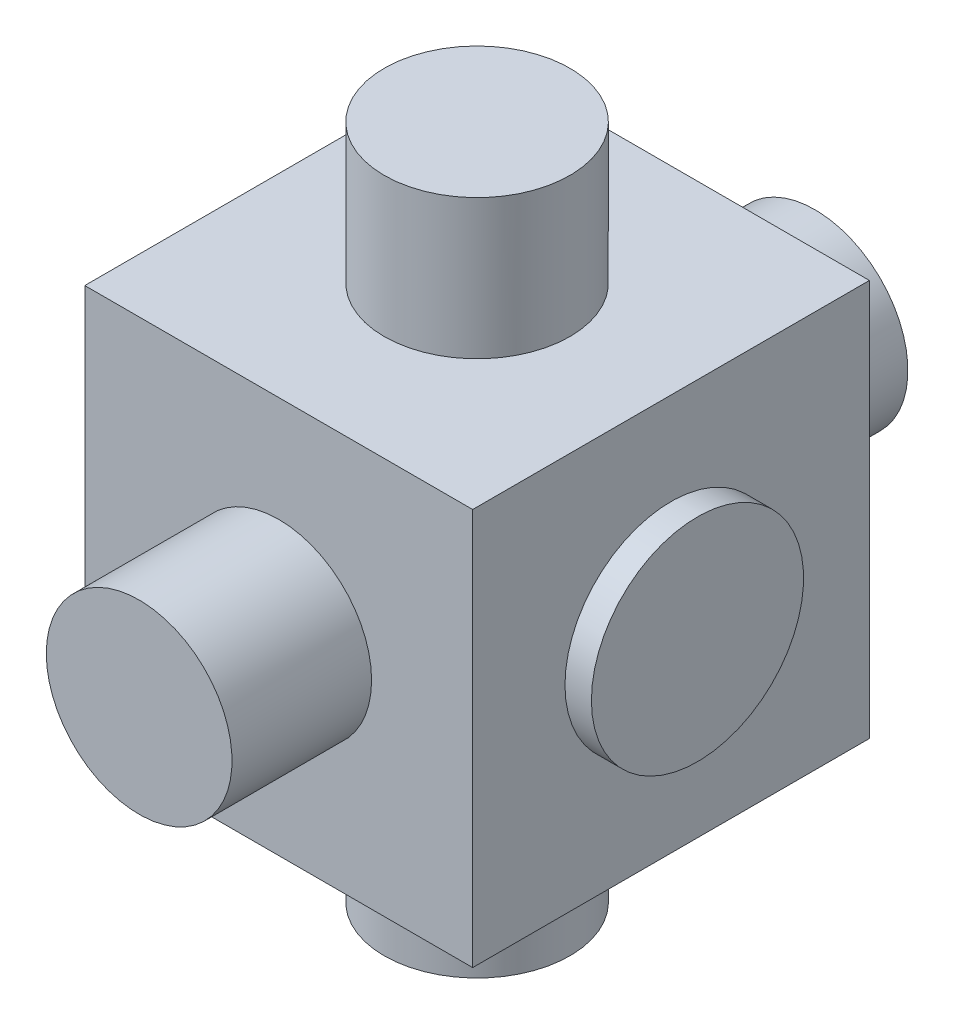
SolidWorks part; units mm, degrees
ref_plane "Front Plane" through (0, 0, 0) normal (0, 0, 1) x (1, 0, 0)
ref_plane "Top Plane" through (0, 0, 0) normal (0, 1, 0) x (1, 0, 0)
ref_plane "Right Plane" through (0, 0, 0) normal (1, 0, 0) x (0, 0, -1)
ref_plane "Plane1" through (0, 0, 0) normal (0, 0, 1) x (1, 0, 0)
sketch "Sketch1" plane through (0, 0, 0) normal (0, 0, 1) x (1, 0, 0)
  line L0 (19.4, 6.75) -> (19.4, -6.75)
  line L1 (19.4, -6.75) -> (32.6, -6.75)
  line L2 (32.6, -6.75) -> (32.6, 6.75)
  line L3 (32.6, 6.75) -> (19.4, 6.75)
extrude "Boss-Extrude1" add sketch "Sketch1" against normal blind 6.75 and the other way blind 6.75
ref_plane "Plane2" through (0, 0, 0) normal (0, 0, 1) x (1, 0, 0)
sketch "Sketch2" plane through (0, 0, 0) normal (0, 0, 1) x (1, 0, 0)
  line L0 (26, 11.5) -> (29.16, 11.5)
  line L1 (29.16, 11.5) -> (29.16, -11.5)
  line L2 (29.16, -11.5) -> (26, -11.5)
  line L3 (26, -11.5) -> (26, 11.5)
  line L4 (26, -11.5) -> (26, 11.5) construction
revolve "Revolve1" add sketch "Sketch2" angle 360 about L4 reverse direction yes
ref_plane "Plane3" through (0, 0, 0) normal (0, 1, 0) x (1, 0, 0)
sketch "Sketch3" plane through (0, 0, 0) normal (0, 1, 0) x (1, 0, 0)
  line L0 (26, 11.5) -> (29.16, 11.5)
  line L1 (29.16, 11.5) -> (29.16, -11.5)
  line L2 (29.16, -11.5) -> (26, -11.5)
  line L3 (26, -11.5) -> (26, 11.5)
  line L4 (26, -11.5) -> (26, 11.5) construction
revolve "Revolve2" add sketch "Sketch3" angle 360 about L4 reverse direction yes
ref_plane "Plane4" through (0, 0, 0) normal (0, 0, 1) x (1, 0, 0)
sketch "Sketch4" plane through (0, 0, 0) normal (0, 0, 1) x (1, 0, 0)
  line L0 (18.5, 0) -> (18.5, 3.61)
  line L1 (18.5, 3.61) -> (33.5, 3.61)
  line L2 (33.5, 3.61) -> (33.5, 0)
  line L3 (33.5, 0) -> (18.5, 0)
  line L4 (33.5, 0) -> (18.5, 0) construction
revolve "Revolve3" add sketch "Sketch4" angle 360 about L4 reverse direction yes
